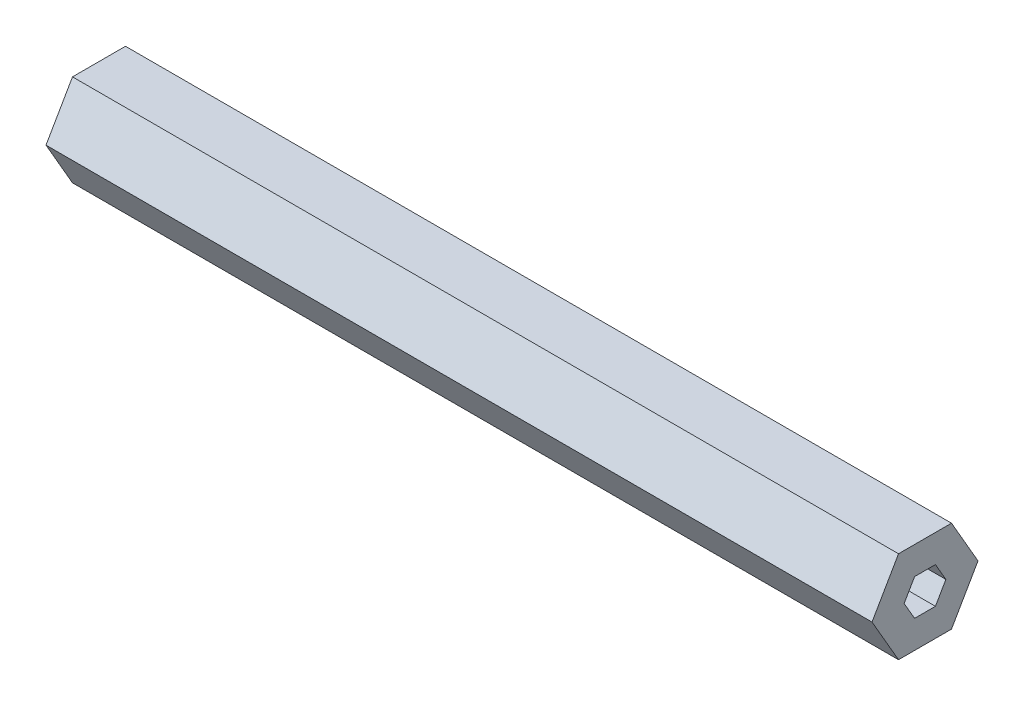
SolidWorks part; units mm, degrees
material "6061-T6 (SS)"
ref_plane "Front" through (0, 0, 0) normal (0, 0, 1) x (1, 0, 0)
ref_plane "Top" through (0, 0, 0) normal (0, 1, 0) x (1, 0, 0)
ref_plane "Right" through (0, 0, 0) normal (1, 0, 0) x (0, 0, -1)
sketch "Sketch1" plane through (0, 0, 0) normal (1, 0, 0) x (0, 0, -1)
  line L1 (7.3323, 0) -> (3.6662, 6.35)
  line L2 (3.6662, 6.35) -> (-3.6662, 6.35)
  line L3 (-3.6662, 6.35) -> (-7.3323, 0)
  line L4 (-7.3323, 0) -> (-3.6662, -6.35)
  line L5 (-3.6662, -6.35) -> (3.6662, -6.35)
  line L6 (3.6662, -6.35) -> (7.3323, 0)
  line L7 (2.8868, 0) -> (1.4434, 2.5)
  line L8 (1.4434, 2.5) -> (-1.4434, 2.5)
  line L9 (-1.4434, 2.5) -> (-2.8868, 0)
  line L10 (-2.8868, 0) -> (-1.4434, -2.5)
  line L11 (-1.4434, -2.5) -> (1.4434, -2.5)
  line L12 (1.4434, -2.5) -> (2.8868, 0)
  circle A0 centre (0, 0) radius 6.35 construction
  circle A1 centre (0, 0) radius 2.5 construction
  dimension "D1" = 12.7
  dimension "D2" = 5
extrude "Boss-Extrude1" add sketch "Sketch1" along normal mid plane 114.3
ref_axis "Axis1" through (-80.9, 0, 0) along (1, 0, 0)
